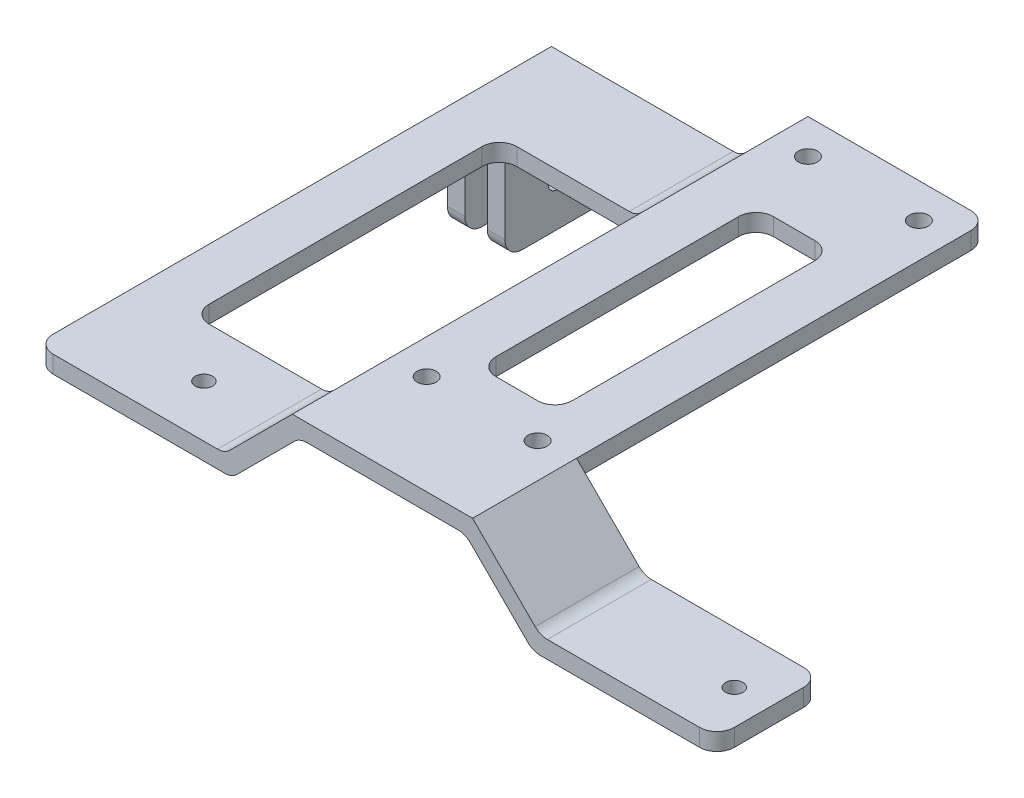
SolidWorks part; units mm, degrees
ref_plane "Front Plane" through (0, 0, 0) normal (0, 0, 1) x (1, 0, 0)
ref_plane "Top Plane" through (0, 0, 0) normal (0, 1, 0) x (1, 0, 0)
ref_plane "Right Plane" through (0, 0, 0) normal (1, 0, 0) x (0, 0, -1)
sketch "Sketch1" plane through (0, 0, 0) normal (0, 1, 0) x (1, 0, 0)
  line L4 (0, 148.75) -> (52, 148.75)
  line L10 (52, 148.75) -> (52, 0)
  line L18 (0, 0) -> (52, 0)
  line L28 (0, 0) -> (0, 148.75)
  line L30 (15, 118.75) -> (37, 118.75)
  line L31 (15, 118.75) -> (15, 38.75)
  line L32 (15, 38.75) -> (37, 38.75)
  line L33 (37, 118.75) -> (37, 38.75)
  circle A0 centre (10, 28.75) radius 2.75
  circle A1 centre (42, 28.75) radius 2.75
  circle A2 centre (10, 138.75) radius 2.75
  circle A3 centre (42, 138.75) radius 2.75
  dimension "D2" = 5.5
  dimension "D3" = 110
  dimension "D4" = 32
  dimension "D5" = 10
  dimension "D6" = 148.75
  dimension "D8" = 10
  dimension "D7" = 10
  dimension "D9" = 30
  dimension "D10" = 10
  dimension "D11" = 15
  dimension "D12" = 15
extrude "Boss-Extrude2" add sketch "Sketch1" along normal blind 5
sketch "Sketch2" plane through (0, 0, 0) normal (0, 0, 1) x (1, 0, 0)
  line L0 (0, 5) -> (0, 0)
  line L1 (-74, -14.5) -> (-74, -19.5)
  line L2 (0, 5) -> (-19.5, -14.5)
  line L3 (-17.4289, -19.5) -> (-74, -19.5)
  line L4 (0, 0) -> (2.0711, 0)
  line L5 (0, 0) -> (52, 0) construction
  line L6 (2.0711, 0) -> (-17.4289, -19.5)
  line L7 (-19.5, -14.5) -> (-74, -14.5)
  line L16 (71.5, -14.5) -> (122.5, -14.5)
  line L17 (49.9289, 0) -> (69.4289, -19.5)
  line L19 (69.4289, -19.5) -> (122.5, -19.5)
  line L20 (52, 5) -> (71.5, -14.5)
  line L21 (122.5, -14.5) -> (122.5, -19.5)
  line L23 (52, 5) -> (52, 0)
  line L24 (52, 0) -> (49.9289, 0)
  line L25 (0, 5) -> (52, 5) construction
  dimension "D1" = 5
  dimension "D2" = 135
  dimension "D3" = 5
  dimension "D4" = 135
  dimension "D5" = 5
  dimension "D6" = 5
  dimension "D7" = 24.5
  dimension "D8" = 24.5
  dimension "D9" = 74
  dimension "D10" = 70.5
extrude "Boss-Extrude3" add sketch "Sketch2" against normal blind 30
sketch "Sketch4" plane through (0, 0, -148.75) normal (0, 0, -1) x (-1, 0, 0)
  line L7 (74, -14.5) -> (74, -44.5)
  line L8 (74, -44.5) -> (69, -44.5)
  line L9 (69, -44.5) -> (69, -19.5)
  line L10 (17.4289, -19.5) -> (-2.0711, 0) construction
  line L11 (-2.0711, 0) -> (0, 0) construction
  line L12 (0, 5) -> (0, 0) construction
  line L13 (0, 5) -> (19.5, -14.5) construction
  line L16 (19.5, -14.5) -> (74, -14.5)
  line L17 (17.4289, -19.5) -> (-2.0711, 0)
  line L18 (-2.0711, 0) -> (0, 0)
  line L19 (0, 5) -> (0, 0)
  line L20 (0, 5) -> (19.5, -14.5)
  line L21 (69, -19.5) -> (62.5, -19.5)
  line L22 (62.5, -19.5) -> (62.5, -44.5)
  line L23 (62.5, -44.5) -> (57.4289, -44.5)
  line L25 (57.4289, -44.5) -> (57.4289, -19.5)
  line L26 (57.4289, -19.5) -> (17.4289, -19.5)
  dimension "D1" = 6.5
  dimension "D2" = 5
  dimension "D3" = 25
  dimension "D4" = 74
  dimension "D5" = 40
extrude "Boss-Extrude5" add sketch "Sketch4" against normal blind 30
sketch "Sketch3" plane through (0, -14.5, 0) normal (0, 1, 0) x (1, 0, 0)
  circle A0 centre (-40.5, 15) radius 2.5
  circle A1 centre (112.5, 15) radius 2.5
  circle A2 centre (10, 28.75) radius 2.75 construction
  circle A3 centre (42, 28.75) radius 2.75 construction
  point P6 (0, 0)
  point P9 (0, 0)
  dimension "D1" = 5
  dimension "D2" = 13.75
  dimension "D3" = 50.5
  dimension "D4" = 70.5
extrude "Cut-Extrude1" cut sketch "Sketch3" against normal up to surface (5 mm away) up to face at (-45.7145, -19.5, -15)
sketch "Sketch5" plane through (-74, 0, 0) normal (-1, 0, 0) x (0, 0, 1)
  line L0 (-118.75, -14.5) -> (-148.75, -14.5) construction
  line L1 (-148.75, -44.5) -> (-148.75, -14.5) construction
  circle A0 centre (-133.75, -32) radius 2.5
  dimension "D1" = 17.5
  dimension "D2" = 5
  dimension "D3" = 15
extrude "Cut-Extrude2" cut sketch "Sketch5" against normal up to surface (16.5711 mm away) up to face at (-57.4289, -32, -133.75)
sketch "Sketch6" plane through (0, -14.5, 0) normal (0, 1, 0) x (1, 0, 0)
  line L0 (-74, 118.75) -> (-74, 30)
  line L1 (-74, 30) -> (-59, 30)
  line L2 (-19.5, 30) -> (-74, 30) construction
  line L3 (-59, 30) -> (-59, 118.75)
  line L4 (-74, 118.75) -> (-19.5, 118.75) construction
  line L5 (-59, 118.75) -> (-74, 118.75)
  dimension "D1" = 15
extrude "Boss-Extrude6" add sketch "Sketch6" against normal blind 5
fillet "Fillet1" radius 5 14 edges at (52, 2.5, -148.75) (37, 2.5, -38.75) (15, 2.5, -38.75) (15, 2.5, -118.75) (37, 2.5, -118.75) (-59, -17, -30) (122.5, -17, -30) (122.5, -17, 0) (-59, -17, -118.75) (-74, -17, 0) (-59.9645, -44.5, -118.75) (-59.9645, -44.5, -148.75) (-71.5, -44.5, -118.75) (-71.5, -44.5, -148.75)
fillet "Fillet2" radius 5 9 edges at (2.0711, 0, -15) (49.9289, 0, -15) (2.0711, 0, -133.75) (-17.4289, -19.5, -133.75) (69.4289, -19.5, -15) (-17.4289, -19.5, -15) (-19.5, -14.5, -133.75) (-19.5, -14.5, -15) (71.5, -14.5, -15)
